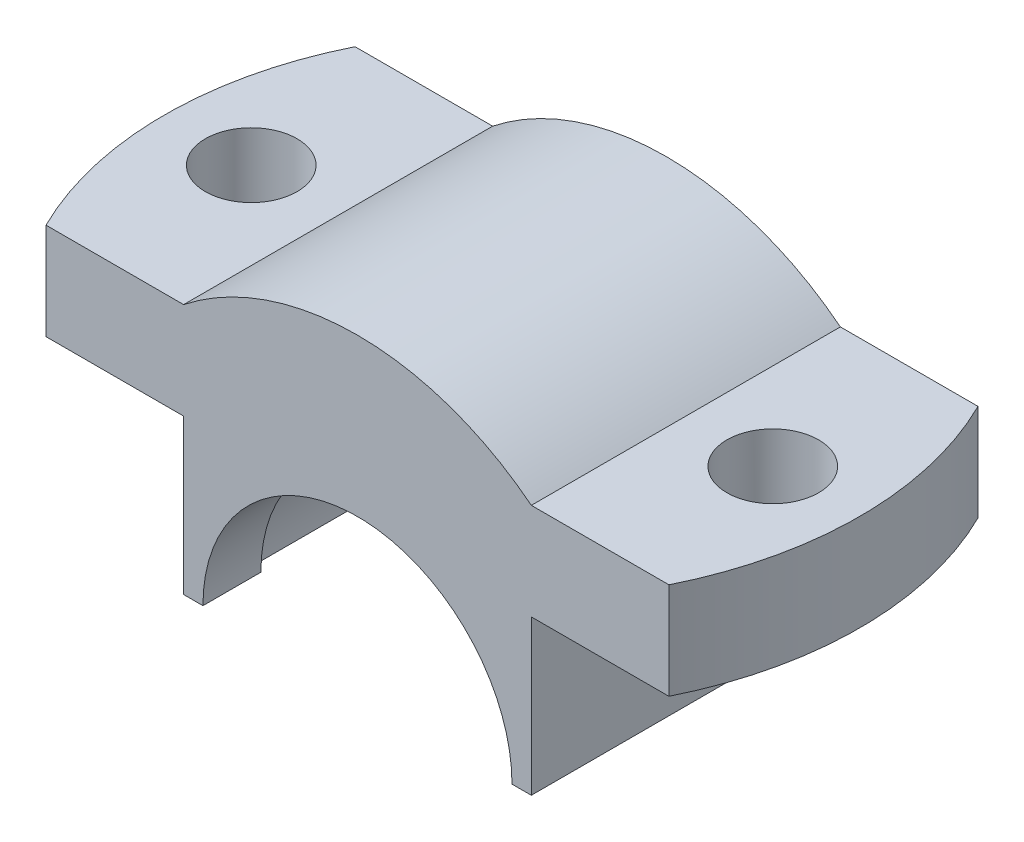
SolidWorks part; units mm, degrees
ref_plane "Front Plane" through (0, 0, 0) normal (0, 0, 1) x (1, 0, 0)
ref_plane "Top Plane" through (0, 0, 0) normal (0, 1, 0) x (1, 0, 0)
ref_plane "Right Plane" through (0, 0, 0) normal (1, 0, 0) x (0, 0, -1)
sketch "Sketch1" plane through (0, 0, 0) normal (0, 0, 1) x (1, 0, 0)
  line L0 (-36, 0) -> (-32, 0)
  line L1 (32, 0) -> (36, 0)
  line L2 (36, 0) -> (36, 32)
  line L3 (-36, 32) -> (-36, 0)
  line L4 (-36, 32) -> (-72, 32)
  line L5 (36, 32) -> (72, 32)
  line L6 (-72, 32) -> (-72, 52)
  line L8 (-72, 52) -> (-36, 52)
  line L9 (72, 52) -> (36, 52)
  line L10 (72, 32) -> (72, 52)
  arc A0 (-36, 52) -> (36, 52) centre (0, 6.5247) cw
  arc A1 (32, 0) -> (-32, 0) centre (0, 0) ccw
  point P7 (0, 0)
  point P10 (0, 32)
  dimension "D1" = 58
  dimension "D2" = 32
  dimension "D5" = 36
  dimension "D6" = 36
  dimension "D3" = 36
  dimension "D4" = 20
extrude "Boss-Extrude1" add sketch "Sketch1" along normal mid plane 64
sketch "Sketch2" plane through (0, 52, 0) normal (0, 1, 0) x (1, 0, 0)
  circle A0 centre (-54, 0) radius 9.5
  circle A1 centre (54, 0) radius 9.5
  dimension "D1" = 9.5
extrude "Cut-Extrude1" cut sketch "Sketch2" against normal blind 64
sketch "Sketch3" plane through (0, 52, 0) normal (0, 1, 0) x (1, 0, 0)
  line L0 (-64.4981, 32) -> (-64.4981, -32)
  line L1 (-36, 32) -> (-72, 32) construction
  line L2 (-36, -32) -> (-72, -32) construction
  line L3 (64.4981, 32) -> (64.4981, -32)
  line L4 (72, 32) -> (36, 32) construction
  line L5 (72, -32) -> (36, -32) construction
  line L6 (-64.4981, 32) -> (-72, 32)
  line L7 (-72, 32) -> (-72, -32)
  line L8 (-72, -32) -> (-64.4981, -32)
  line L9 (64.4981, 32) -> (72, 32)
  line L10 (72, 32) -> (72, -32)
  line L11 (72, -32) -> (64.4981, -32)
  arc A0 (-64.4981, 32) -> (-64.4981, -32) centre (0, 0) ccw
  arc A1 (64.4981, -32) -> (64.4981, 32) centre (0, 0) ccw
  line M2 (72, 32) -> (36, 32)
  line M4 (36, -32) -> (72, -32)
  line M5 (72, -32) -> (72, 32)
  dimension "D1" = 72
extrude "Cut-Extrude2" cut sketch "Sketch3" against normal blind 22 contours A0 L6 L7 | A0 L7 L8 | A1 L10 M2 | A1 M4 M5 region at (-69.7711, 52, -24.0857) region at (-69.7711, 52, 24.0857) region at (69.7711, 52, -24.0857) region at (69.7711, 52, 24.0857)
sketch "Sketch5" plane through (0, 0, -32) normal (0, 0, -1) x (-1, 0, 0)
  line L0 (-34, 0) -> (-32, 0)
  line L1 (32, 0) -> (34, 0)
  arc A0 (34, 0) -> (-34, 0) centre (0, 0) ccw
  arc A1 (32, 0) -> (-32, 0) centre (0, 0) ccw
  dimension "D1" = 34
extrude "Cut-Extrude3" cut sketch "Sketch5" against normal blind 38 from offset 12 contours A0 L0 A1 L1 offset against normal yes
chamfer "Chamfer1" distance 2 angle 45 2 edges at (0, 32, 18) (0, 32, -20)
